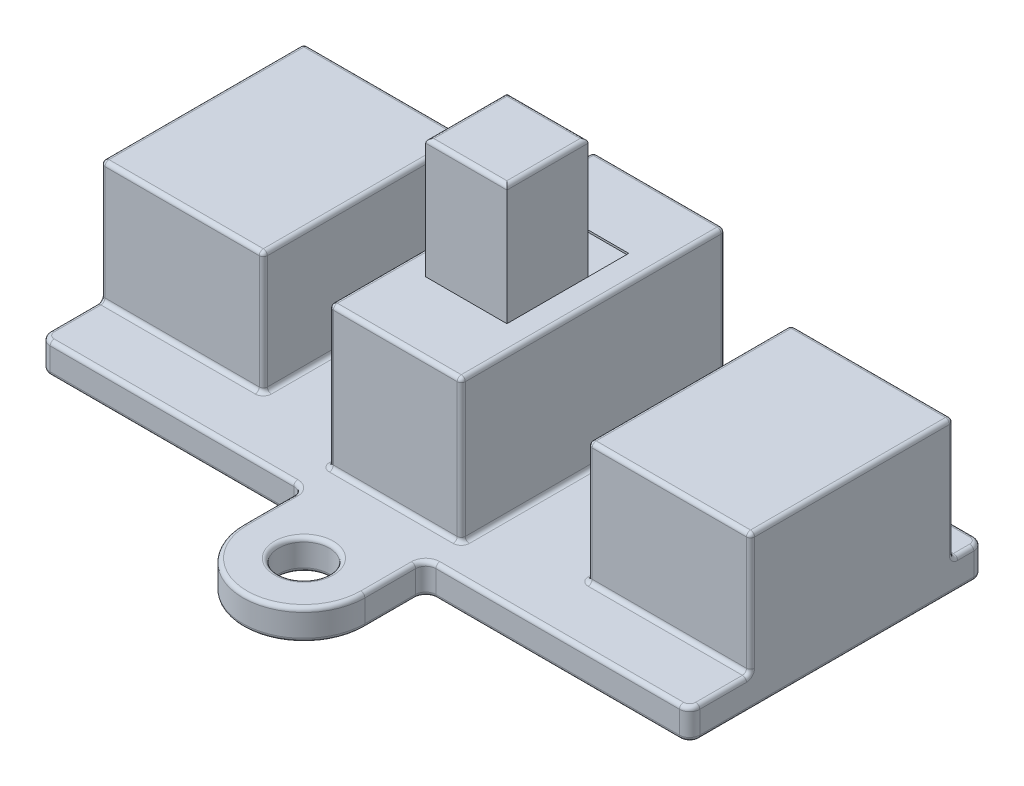
SolidWorks part; units mm, degrees
ref_plane "前视基准面" through (0, 0, 0) normal (0, 0, 1) x (1, 0, 0)
ref_plane "上视基准面" through (0, 0, 0) normal (0, 1, 0) x (1, 0, 0)
ref_plane "右视基准面" through (0, 0, 0) normal (1, 0, 0) x (0, 0, -1)
other "Configuration Table"
ref_axis "基准轴1" through (0, -46.8641, 0) along (0, 1, 0)
sketch "草图1" plane through (0, 0, 0) normal (0, 1, 0) x (1, 0, 0)
  line L2 (-3, 0) -> (-3, 3)
  line L3 (-16, 17.5) -> (16, 17.5)
  line L4 (-16, 17.5) -> (-16, 3)
  line L5 (-16, 3) -> (16, 3)
  line L6 (16, 17.5) -> (16, 3)
  line L7 (3, 0) -> (3, 3)
  line L8 (0, 0) -> (0, 17.5) construction
  circle A3 centre (0, 0) radius 1.25
  circle A4 centre (0, 0) radius 3
  dimension "D1" = 2.5
  dimension "D2" = 6
  dimension "D3" = 14.5
  dimension "D4" = 32
extrude "凸台-拉伸-PCB板" add sketch "草图1" along normal blind 1.5 contours L8 L5 L6 L3 | L5 L8 L3 L4 | A4 L5 L2 | A4 L7 L5 | A3 A4 region at (-2.0613, 0, -2.0613) region at (-2.3299, 0, -2.3299) region at (-8, 0, -10.25) region at (2.3299, 0, -2.3299) region at (8, 0, -10.25)
sketch "草图2" plane through (0, 1.5, 0) normal (0, 1, 0) x (1, 0, 0)
  line L0 (-16, 17.5) -> (-16, 3) construction
  line L1 (-16, 16) -> (-8, 16)
  line L2 (-16, 16) -> (-16, 6)
  line L3 (-16, 6) -> (-8, 6)
  line L4 (-8, 16) -> (-8, 6)
  line L5 (0, 0) -> (0, 19.7459) construction
  line L6 (-16, 3) -> (-3, 3) construction
  line L7 (16, 6) -> (8, 6)
  line L8 (8, 16) -> (8, 6)
  line L9 (16, 16) -> (8, 16)
  line L10 (16, 16) -> (16, 6)
  dimension "D1" = 10
  dimension "D2" = 8
  dimension "D3" = 3
extrude "凸台-拉伸-插座" add sketch "草图2" along normal blind 6
sketch "草图3" plane through (0, 1.5, 0) normal (0, 1, 0) x (1, 0, 0)
  line L0 (-16, 17.5) -> (16, 17.5) construction
  line L1 (-3.25, 17.5) -> (3.25, 17.5)
  line L2 (-3.25, 17.5) -> (-3.25, 4.5)
  line L3 (-3.25, 4.5) -> (3.25, 4.5)
  line L4 (3.25, 17.5) -> (3.25, 4.5)
  line L5 (0, 0) -> (0, 4.5) construction
  dimension "D1" = 13
  dimension "D2" = 6.5
extrude "凸台-拉伸-开关底座" add sketch "草图3" along normal blind 7
sketch "草图4" plane through (0, 8.5, 0) normal (0, 1, 0) x (1, 0, 0)
  line L0 (0, 0) -> (0, 8) construction
  line L1 (-2, 14) -> (2, 14)
  line L2 (-2, 14) -> (-2, 8)
  line L3 (-2, 8) -> (2, 8)
  line L4 (2, 14) -> (2, 8)
  line L5 (-3.25, 11) -> (-2, 11) construction
  line L6 (-3.25, 17.5) -> (-3.25, 4.5) construction
  dimension "D1" = 4
  dimension "D2" = 6
extrude "切除-拉伸1" cut sketch "草图4" against normal blind 0.1
sketch "草图5" plane through (0, 8.4, 0) normal (0, 1, 0) x (1, 0, 0)
  line L0 (2, 8) -> (2, 14) construction
  line L1 (-2, 8) -> (2, 8)
  line L2 (-2, 8) -> (-2, 12)
  line L3 (-2, 12) -> (2, 12)
  line L4 (2, 8) -> (2, 12)
  dimension "D1" = 4
extrude "凸台-拉伸-拨杆" add sketch "草图5" along normal blind 6
fillet "圆角1" radius 0.5 6 edges at (-16, 0.75, -17.5) (-3, 0.75, -3) (-16, 0.75, -3) (3, 0.75, -3) (16, 0.75, -17.5) (16, 0.75, -3)
fillet "圆角2" radius 0.2 70 edges at (-3.25, 5, -17.5) (3.25, 5, -17.5) (16, 4.5, -16) (16, 4.5, -6) (-16, 4.5, -6) (-16, 4.5, -16) (0, 14.4, -12) (2, 14.4, -10) (0, 14.4, -8) (-2, 14.4, -10) (8, 4.5, -16) (8, 4.5, -6) (-8, 4.5, -6) (-8, 4.5, -16) (-3.25, 5, -4.5) (0, 8.5, -4.5) (3.25, 5, -4.5) (12, 7.5, -6) (8, 7.5, -11) (12, 7.5, -16) (16, 7.5, -11) (-12, 7.5, -16) (-8, 7.5, -11) (-12, 7.5, -6) (-16, 7.5, -11) (-3.25, 1.5, -11) (0, 1.5, -4.5) (3.25, 1.5, -11) (9.375, 1.5, -17.5) (15.8536, 1.5, -17.3536) (16, 1.5, -16.5) (12, 1.5, -16) (8, 1.5, -11) (12, 1.5, -6) (16, 1.5, -4.75) (15.8536, 1.5, -3.1464) (9.5, 1.5, -3) (3.1464, 1.5, -2.8536) (3, 1.5, -1.25) (0, 1.5, 3) (-3, 1.5, -1.25) (-3.1464, 1.5, -2.8536) (-9.5, 1.5, -3) (-15.8536, 1.5, -3.1464) (-16, 1.5, -4.75) (-12, 1.5, -6) (-8, 1.5, -11) (-12, 1.5, -16) (-16, 1.5, -16.5) (-15.8536, 1.5, -17.3536) (-9.375, 1.5, -17.5) (0, 1.5, 1.25) (0, 0, 1.25) (-15.8536, 0, -3.1464) (-9.5, 0, -3) (-3.1464, 0, -2.8536) (-3, 0, -1.25) (0, 0, 3) (3, 0, -1.25) (3.1464, 0, -2.8536) (9.5, 0, -3) (15.8536, 0, -3.1464) (16, 0, -10.25) (15.8536, 0, -17.3536) (0, 0, -17.5) (-15.8536, 0, -17.3536) (-16, 0, -10.25) (0, 8.5, -17.5) (-3.25, 8.5, -11) (3.25, 8.5, -11)
